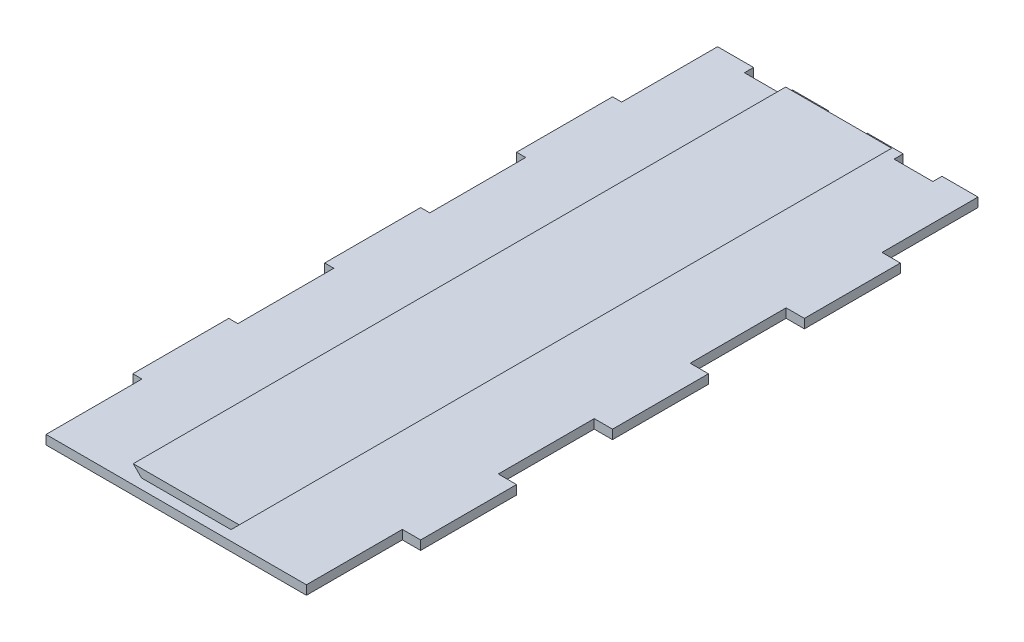
SolidWorks part; units mm, degrees
ref_plane "前视基准面" through (0, 0, 0) normal (0, 0, 1) x (1, 0, 0)
ref_plane "上视基准面" through (0, 0, 0) normal (0, 1, 0) x (1, 0, 0)
ref_plane "右视基准面" through (0, 0, 0) normal (1, 0, 0) x (0, 0, -1)
other "Configuration Table"
sketch "草图4" plane through (0, 0, 0) normal (0, 1, 0) x (1, 0, 0)
  line L6 (-28.5, -72.5) -> (28.5, -72.5)
  line L11 (-28.5, -72.5) -> (-28.5, 72.5)
  line L12 (-28.5, 72.5) -> (28.5, 72.5)
  line L13 (28.5, -72.5) -> (28.5, 72.5)
  line L14 (-28.5, -72.5) -> (28.5, 72.5) construction
  line L15 (-28.5, 72.5) -> (28.5, -72.5) construction
  point P0 (0, 0)
  dimension "D1" = 57
  dimension "D2" = 145
extrude "凸台-拉伸1" add sketch "草图4" along normal blind 2
sketch "草图5" plane through (0, 0, -72.5) normal (0, 0, -1) x (-1, 0, 0)
  line L0 (-28.5, 2) -> (28.5, 2) construction
  line L1 (28.5, 0) -> (20.625, 0)
  line L2 (28.5, 0) -> (28.5, 2)
  line L3 (28.5, 2) -> (20.625, 2)
  line L4 (20.625, 0) -> (20.625, 2)
  line L5 (-28.5, 0) -> (28.5, 0) construction
  line L6 (12.125, 0) -> (4.25, 0)
  line L7 (12.125, 0) -> (12.125, 2)
  line L8 (12.125, 2) -> (4.25, 2)
  line L9 (4.25, 0) -> (4.25, 2)
  line L10 (20.625, 0) -> (12.125, 0)
  line L11 (-4.25, 0) -> (-12.125, 0)
  line L12 (-4.25, 0) -> (-4.25, 2)
  line L13 (-4.25, 2) -> (-12.125, 2)
  line L14 (-12.125, 0) -> (-12.125, 2)
  line L15 (-20.625, 0) -> (-28.5, 0)
  line L16 (-20.625, 0) -> (-20.625, 2)
  line L17 (-20.625, 2) -> (-28.5, 2)
  line L18 (-28.5, 0) -> (-28.5, 2)
  line L19 (4.25, 0) -> (-4.25, 0)
  line L20 (-12.125, 0) -> (-20.625, 0)
  line M17 (-28.5, 0) -> (28.5, 0)
  line M18 (28.5, 0) -> (28.5, 2)
  line M19 (28.5, 2) -> (-28.5, 2)
  line M20 (-28.5, 2) -> (-28.5, 0)
  dimension "D1" = 8.5
extrude "凸台-拉伸2" add sketch "草图5" along normal blind 2 contours L16 M17 M19 M20 | L14 L12 M17 M19 | L9 L7 M17 M19 | L4 M17 M18 M19 region at (-24.5625, 1, -72.5) region at (-8.1875, 1, -72.5) region at (8.1875, 1, -72.5) region at (24.5625, 1, -72.5)
sketch "草图6" plane through (-28.5, 0, 0) normal (-1, 0, 0) x (0, 0, 1)
  line L0 (-74.5, 2) -> (72.5, 2) construction
  line L1 (-53.5, 2) -> (-32.5, 2)
  line L2 (-53.5, 2) -> (-53.5, 0)
  line L3 (-53.5, 0) -> (-32.5, 0)
  line L4 (-32.5, 2) -> (-32.5, 0)
  line L5 (-74.5, 0) -> (72.5, 0) construction
  line L6 (-74.5, 1) -> (-53.5, 1) construction
  line L7 (-11.5, 2) -> (9.5, 2)
  line L8 (-11.5, 2) -> (-11.5, 0)
  line L9 (-11.5, 0) -> (9.5, 0)
  line L10 (9.5, 2) -> (9.5, 0)
  line L11 (30.5, 2) -> (51.5, 2)
  line L12 (30.5, 2) -> (30.5, 0)
  line L13 (30.5, 0) -> (51.5, 0)
  line L14 (51.5, 2) -> (51.5, 0)
  line L15 (-74.5, 0) -> (-74.5, 2) construction
  line L16 (-53.5, 1) -> (-32.5, 1) construction
  line L17 (-32.5, 1) -> (-11.5, 1) construction
  line L18 (-11.5, 1) -> (9.5, 1) construction
  line L19 (9.5, 1) -> (30.5, 1) construction
  line L20 (30.5, 1) -> (51.5, 1) construction
  line L21 (51.5, 1) -> (72.5, 1) construction
  line L22 (72.5, 2) -> (72.5, 0) construction
extrude "凸台-拉伸3" add sketch "草图6" along normal blind 2
extrude "凸台-拉伸4" add sketch "草图6<2>" against normal blind 4 from surface starting at face at (28.5, 1, -1)
sketch "草图6<2>" plane through (-28.5, 0, 0) normal (-1, 0, 0) x (0, 0, 1) same geometry as "草图6"
sketch "草图7" plane through (0, 2, 0) normal (0, 1, 0) x (1, 0, 0)
  line L0 (0, 0) -> (0, 54.1824) construction
  line L1 (-16.375, 72.5) -> (-10, 52.5)
  line L2 (-12.125, 72.5) -> (-20.625, 72.5) construction
  line L3 (-10, 52.5) -> (-10, -72.5)
  line L4 (-28.5, -72.5) -> (28.5, -72.5) construction
  line L5 (16.375, 72.5) -> (10, 52.5)
  line L6 (20.625, 72.5) -> (12.125, 72.5) construction
  line L7 (10, 52.5) -> (10, -72.5)
  line L8 (-10, 52.5) -> (0, 52.5)
  line L9 (0, 52.5) -> (10, 52.5)
  dimension "D1" = 20
  dimension "D2" = 10
sketch "草图8" plane through (0, 0, 72.5) normal (0, 0, 1) x (1, 0, 0)
  line L0 (-9.8, 2) -> (-11.6, 3.8)
  line L1 (-10, 2) -> (0, 2) construction
  line L3 (9.8, 2) -> (9.8, 3.8) construction
  line L4 (11.6, 3.8) -> (9.8, 2)
  line L5 (0, 2) -> (10, 2) construction
  line L6 (16.375, 2) -> (10, 2) construction
  line L7 (-9.8, 2) -> (-9.8, 3.8) construction
  line L8 (-11.6, 3.8) -> (-9.8, 3.8)
  line L9 (-9.8, 3.8) -> (9.8, 3.8)
  line L10 (9.8, 3.8) -> (11.6, 3.8)
  line L11 (0, 3.8) -> (0, 2) construction
  line M12 (28.5, 2) -> (-28.5, 2)
  dimension "D1" = 1.8
  dimension "D2" = 19.6
extrude "凸台-拉伸5" add sketch "草图8" against normal up to surface (145 mm away) from offset 2.2 contours L10 L9 L8 L0 L4 M12 region at (0, 2.9252, 72.5) up to face at (16.375, 1, -72.5) offset against normal yes
